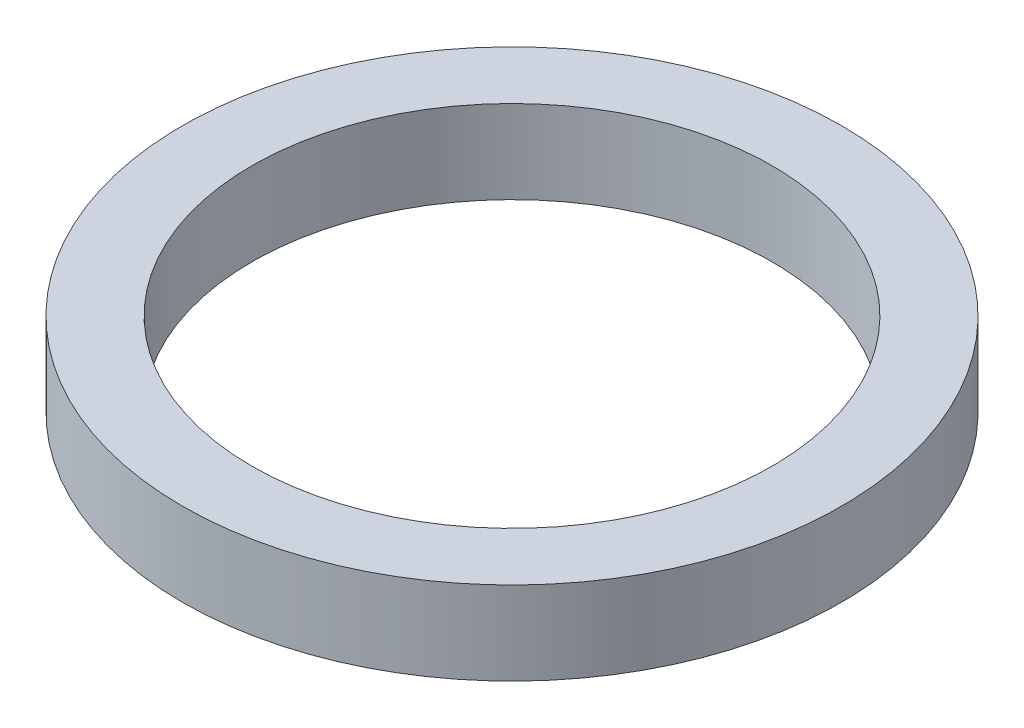
SolidWorks part; units mm, degrees
ref_plane "Front Plane" through (0, 0, 0) normal (0, 0, 1) x (1, 0, 0)
ref_plane "Top Plane" through (0, 0, 0) normal (0, 1, 0) x (1, 0, 0)
ref_plane "Right Plane" through (0, 0, 0) normal (1, 0, 0) x (0, 0, -1)
sketch "Sketch1" plane through (0, 0, 0) normal (0, 1, 0) x (1, 0, 0)
  circle A0 centre (0, 0) radius 47.5
  dimension "FLANGE_OD" = 95
extrude "Boss-Extrude1" add sketch "Sketch1" along normal blind 12
sketch "Sketch2" plane through (0, 0, 0) normal (0, 1, 0) x (1, 0, 0)
  circle A0 centre (0, 0) radius 37.5
  dimension "BORE_D" = 75
extrude "Cut-Extrude1" cut sketch "Sketch2" along normal through all
sketch "Sketch3" plane through (0, 12, 0) normal (0, 1, 0) x (1, 0, 0)
  circle A0 centre (0, 0) radius 22.0681 construction
  circle A1 centre (-22.0681, 0) radius 1.5854
  dimension "BOLT_D" = 3.1708
  dimension "BOLT_PCD" = 44.1363
extrude "Cut-Extrude2" cut sketch "Sketch3" against normal blind 8.673 rebuild error yes
pattern_circular "CirPattern1" count 3 over 360 rebuild error yes
